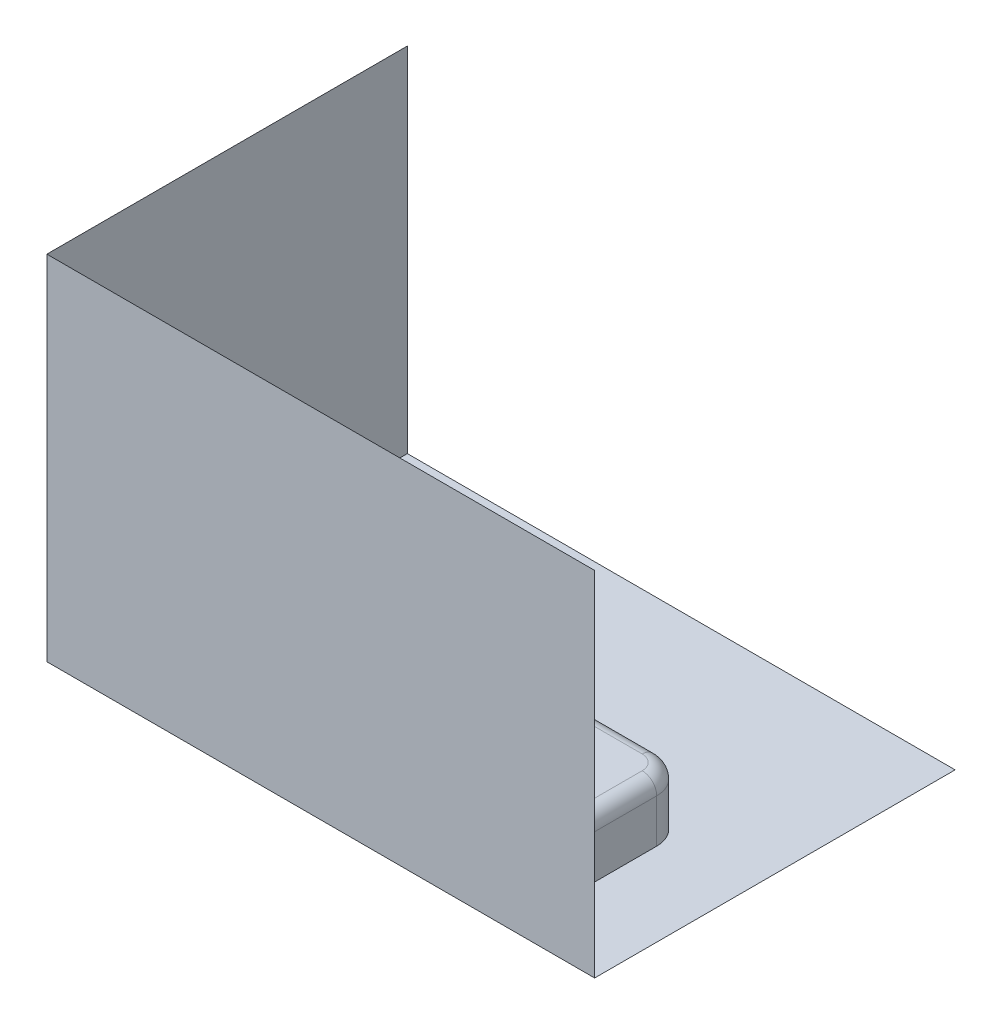
SolidWorks part; units mm, degrees
ref_plane "Plane1" through (0, 0, 0) normal (0, 0, 1) x (1, 0, 0)
ref_plane "Plane2" through (0, 0, 0) normal (0, 1, 0) x (1, 0, 0)
ref_plane "Plane3" through (0, 0, 0) normal (1, 0, 0) x (0, 0, -1)
sketch "Sketch1" plane through (0, 0, 0) normal (0, 1, 0) x (1, 0, 0)
  line L1 (0, 0) -> (101.6, 0)
  line L2 (0, 0) -> (0, 38.1)
  line L3 (0, 38.1) -> (101.6, 38.1)
  line L4 (101.6, 0) -> (101.6, 38.1)
  dimension "D1" = 101.6
  dimension "D2" = 38.1
extrude "Base-Extrude" add sketch "Sketch1" along normal blind 12.7
sketch "Sketch2" plane through (0, 0, 0) normal (0, 0, 1) x (1, 0, 0)
  line L0 (50.8, 0) -> (50.8, 66.8931) construction
  line L1 (0, 0) -> (101.6, 0) construction
  line L2 (31.75, 0) -> (31.75, 38.1)
  line L3 (69.85, 38.1) -> (69.85, 0)
  line L4 (69.85, 0) -> (31.75, 0)
  arc A0 (31.75, 38.1) -> (69.85, 38.1) centre (50.8, 38.1) cw
  dimension "D1" = 19.05
  dimension "D2" = 38.1
extrude "Boss-Extrude1" add sketch "Sketch2" against normal blind 12.7
hole_wizard "CBORE for 1/4 Hex Head Bolt1" positions "Sketch8" profile "Sketch9" counterbore size "1/4" standard "Ansi Inch" end condition through all
sketch "Sketch8" plane through (1.1036, -5.641, 0) normal (0, 0, 1) x (1, 0, 0)
  point P0 (49.6964, 43.741)
sketch "Sketch9" plane through (50.8, 38.1, 0) normal (1, 0, 0) x (0, -1, 0)
  line L0 (0, 0) -> (0, 38.1)
  line L1 (0, 38.1) -> (3.3782, 38.1)
  line L3 (3.3782, 38.1) -> (3.3782, 4.7752)
  line L4 (3.3782, 4.7752) -> (9.525, 4.7752)
  line L5 (9.525, 4.7752) -> (9.525, 0)
  line L7 (9.525, 0) -> (0, 0)
  line L11 (0, -6.35) -> (0, 107.95) construction
  dimension "Thru Hole Dia." = 6.7564
  dimension "Thru Hole Depth" = 38.1
  dimension "C'Bore Dia." = 19.05
  dimension "C'Bore Depth" = 4.7752
sketch "Sketch10" plane through (-1.0713, 1.1621, 0) normal (0, 0, 1) x (1, 0, 0)
  line L1 (32.8213, -1.1621) -> (70.9213, -1.1621)
  line L2 (32.8213, -1.1621) -> (32.8213, 2.0129)
  line L3 (32.8213, 2.0129) -> (70.9213, 2.0129)
  line L4 (70.9213, -1.1621) -> (70.9213, 2.0129)
  line L8 (70.9213, 11.5379) -> (70.9213, 36.9379) construction
  line L9 (32.8213, 36.9379) -> (32.8213, 11.5379) construction
  line L11 (1.0713, -1.1621) -> (102.6713, -1.1621) construction
  dimension "D1" = 3.175
extrude "Cut-Extrude1" cut sketch "Sketch10" against normal through all
hole_wizard "9/32 (0.28125) Diameter Hole1" positions "Sketch11" profile "Sketch12" hole size "9/32" standard "Ansi Inch" end condition through all
sketch "Sketch11" plane through (45.9081, 12.7, 7.8552) normal (0, 1, 0) x (-1, 0, 0)
  line L4 (45.9081, -45.9552) -> (45.9081, -7.8552) construction
  line L6 (-55.6919, -7.8552) -> (-55.6919, -45.9552) construction
  line L7 (-55.6919, -45.9552) -> (45.9081, -45.9552) construction
  point P0 (-42.9919, -33.2552)
  point P1 (33.2081, -33.2552)
  dimension "D1" = 12.7
  dimension "D2" = 12.7
  dimension "D3" = 12.7
sketch "Sketch12" plane through (88.9, 12.7, -25.4) normal (1, 0, 0) x (0, 0, 1)
  line L0 (0, 0) -> (0, 12.7)
  line L1 (0, 12.7) -> (3.5719, 12.7)
  line L2 (3.5719, 12.7) -> (3.5719, 0)
  line L5 (3.5719, 0) -> (0, 0)
  line L11 (0, -6.35) -> (0, 107.95) construction
  dimension "Thru Hole Dia." = 7.1437
  dimension "Thru Hole Depth" = 12.7
fillet "Fillet1" radius 6.35 10 edges at (31.75, 1.5875, -38.1) (31.75, 3.175, -19.05) (69.85, 1.5875, -38.1) (69.85, 3.175, -19.05) (31.75, 1.5875, 0) (69.85, 1.5875, 0) (0, 6.35, -38.1) (101.6, 6.35, -38.1) (101.6, 6.35, 0) (0, 6.35, 0)
fillet "Fillet2" radius 3.175 18 edges at (82.55, 12.7, 0) (31.75, 25.4, -12.7) (69.85, 25.4, -12.7) (31.75, 25.4, 0) (69.85, 25.4, 0) (50.8, 57.15, 0) (31.75, 12.7, -6.35) (50.8, 57.15, -12.7) (69.85, 12.7, -6.35) (50.8, 12.7, -12.7) (19.05, 12.7, 0) (0, 12.7, -19.05) (101.6, 12.7, -19.05) (50.8, 12.7, -38.1) (1.8599, 12.7, -36.2401) (99.7401, 12.7, -36.2401) (99.7401, 12.7, -1.8599) (1.8599, 12.7, -1.8599)
sketch "Sketch5" plane through (0, 0, 0) normal (0, 0, -1) x (-1, 0, 0)
  line L0 (0, 0) -> (0, 9.525) construction
  line L1 (0, 77.1809) -> (-119.7743, 77.1809)
  line L2 (0, 77.1809) -> (0, 0)
  line L3 (0, 0) -> (-119.7743, 0)
  line L4 (-119.7743, 77.1809) -> (-119.7743, 0)
  line L5 (-6.35, 0) -> (-31.75, 0) construction
surface "Surface-Plane1" sketch "Sketch5"
sketch "Sketch6" plane through (0, 0, 0) normal (-1, 0, 0) x (0, 0, 1)
  line L1 (-78.8266, 77.1809) -> (0, 77.1809)
  line L2 (-78.8266, 77.1809) -> (-78.8266, 0)
  line L3 (-78.8266, 0) -> (0, 0)
  line L4 (0, 77.1809) -> (0, 0)
surface "Surface-Plane2" sketch "Sketch6"
sketch "Sketch7" plane through (0, 0, 0) normal (0, -1, 0) x (1, 0, 0)
  line L1 (0, 0) -> (119.7743, 0)
  line L2 (0, 0) -> (0, -78.8266)
  line L3 (0, -78.8266) -> (119.7743, -78.8266)
  line L4 (119.7743, 0) -> (119.7743, -78.8266)
surface "Surface-Plane3" sketch "Sketch7"
